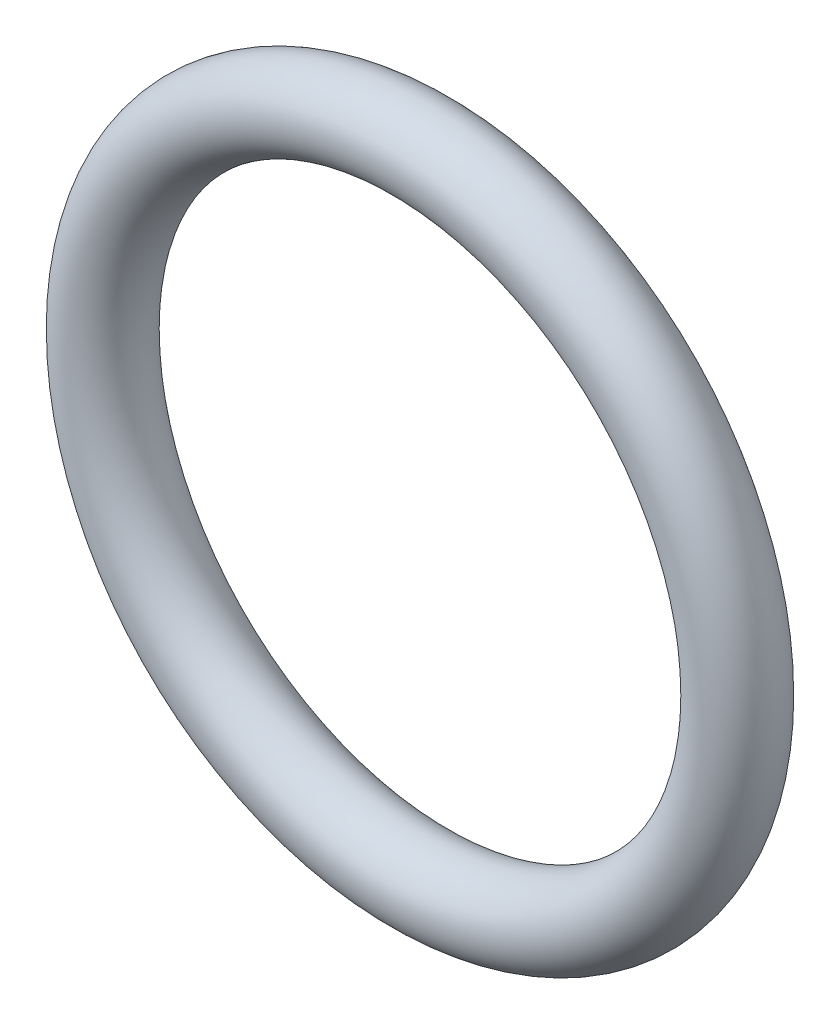
SolidWorks part; units mm, degrees
ref_plane "Front" through (0, 0, 0) normal (0, 0, 1) x (1, 0, 0)
ref_plane "Top" through (0, 0, 0) normal (0, 1, 0) x (1, 0, 0)
ref_plane "Right" through (0, 0, 0) normal (1, 0, 0) x (0, 0, -1)
sketch "Sketch1" plane through (0, 0, 0) normal (0, 0, 1) x (1, 0, 0)
  circle A0 centre (0, 0) radius 6.25
  dimension "d1" = 12.5
sketch "Sketch2" plane through (0, 0, 0) normal (0, 1, 0) x (1, 0, 0)
  circle A0 centre (-7.15, 0) radius 0.9
  point P2 (-6.25, 0)
  dimension "d2" = 1.8
sweep "Sweep1" add profiles "Sketch2" path "Sketch1"
ref_axis "Axis1" through (0, 0, -4.6197) along (0, 0, 1)
